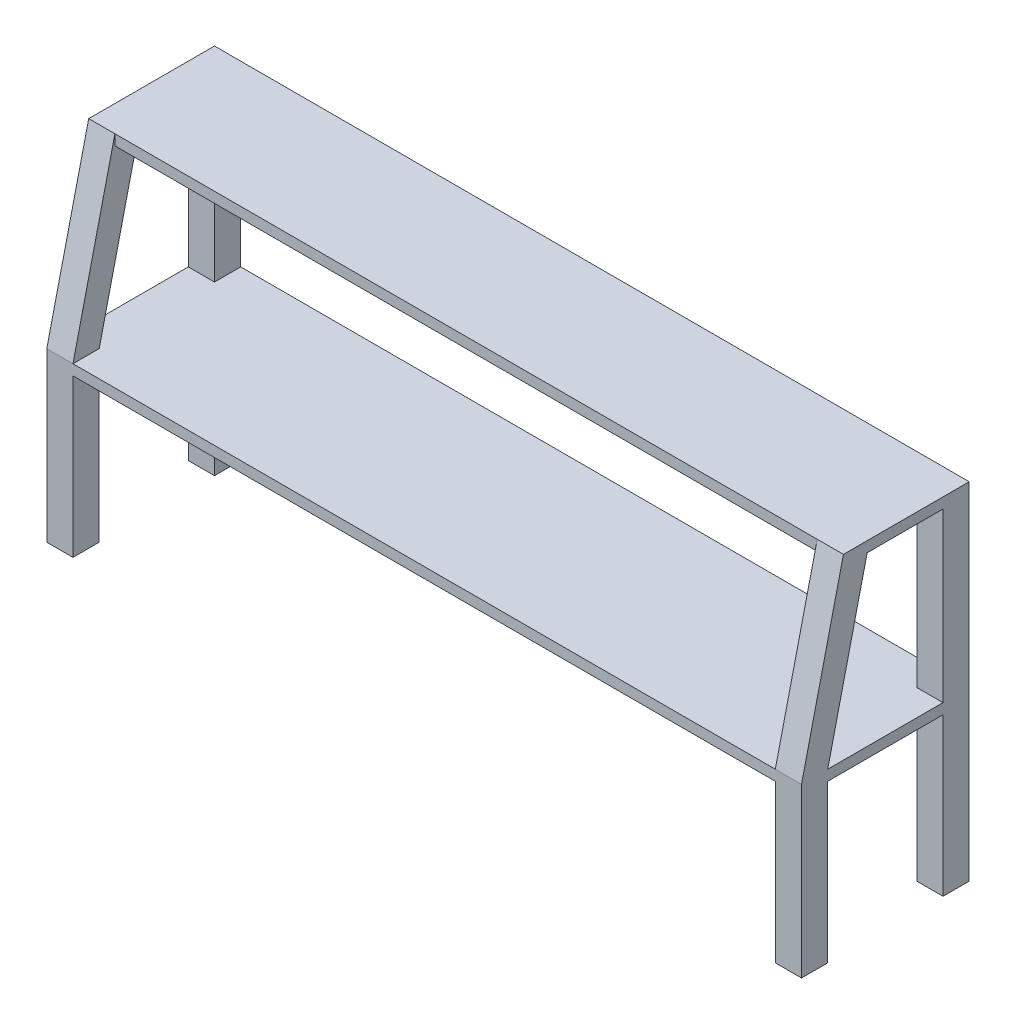
SolidWorks part; units mm, degrees
ref_plane "Front Plane" through (0, 0, 0) normal (0, 0, 1) x (1, 0, 0)
ref_plane "Top Plane" through (0, 0, 0) normal (0, 1, 0) x (1, 0, 0)
ref_plane "Right Plane" through (0, 0, 0) normal (1, 0, 0) x (0, 0, -1)
sketch "Sketch1" plane through (0, 0, 0) normal (0, 1, 0) x (1, 0, 0)
  line L1 (0, 0) -> (914.4, 0)
  line L2 (0, 0) -> (0, 203.2)
  line L3 (0, 203.2) -> (914.4, 203.2)
  line L4 (914.4, 0) -> (914.4, 203.2)
  dimension "D1" = 203.2
  dimension "D2" = 914.4
extrude "Boss-Extrude1" add sketch "Sketch1" along normal blind 12.7
ref_plane "Plane1" through (0, 215.9, 0) normal (0, 1, 0) x (1, 0, 0)
sketch "Sketch2" plane through (0, 215.9, 0) normal (0, 1, 0) x (1, 0, 0)
  line L0 (0, 203.2) -> (0, 0) construction
  line L1 (914.4, 203.2) -> (0, 203.2)
  line L2 (914.4, 203.2) -> (914.4, 50.8)
  line L3 (914.4, 50.8) -> (0, 50.8)
  line L4 (0, 203.2) -> (0, 50.8)
  dimension "D1" = 152.4
extrude "Boss-Extrude2" add sketch "Sketch2" along normal blind 12.7 separate body
sketch "Sketch3" plane through (914.4, 0, 0) normal (1, 0, 0) x (0, 0, -1)
  line L1 (203.2, 228.6) -> (171.45, 228.6)
  line L2 (203.2, 228.6) -> (203.2, -190.5)
  line L3 (203.2, -190.5) -> (171.45, -190.5)
  line L4 (171.45, 228.6) -> (171.45, -190.5)
  line L5 (0, 12.7) -> (203.2, 12.7) construction
  line L6 (0, 12.7) -> (0, -190.5)
  line L7 (0, -190.5) -> (31.75, -190.5)
  line L8 (31.75, -190.5) -> (31.75, 12.7)
  line L9 (0, 12.7) -> (50.8, 228.6)
  line L10 (50.8, 228.6) -> (82.55, 228.6)
  line L11 (50.8, 228.6) -> (203.2, 228.6) construction
  line L12 (82.55, 228.6) -> (31.75, 12.7)
  dimension "D1" = 203.2
  dimension "D2" = 31.75
extrude "Boss-Extrude3" add sketch "Sketch3" against normal blind 31.75
extrude "Boss-Extrude4" add sketch "Sketch3<2>" along normal blind 31.75 from surface starting at face at (0, 6.35, -101.6)
sketch "Sketch3<2>" plane through (914.4, 0, 0) normal (1, 0, 0) x (0, 0, -1) same geometry as "Sketch3"
